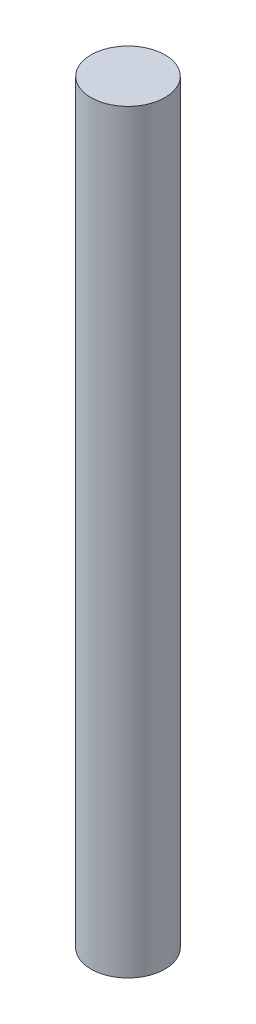
SolidWorks part; units mm, degrees
ref_plane "Front Plane" through (0, 0, 0) normal (0, 0, 1) x (1, 0, 0)
ref_plane "Top Plane" through (0, 0, 0) normal (0, 1, 0) x (1, 0, 0)
ref_plane "Right Plane" through (0, 0, 0) normal (1, 0, 0) x (0, 0, -1)
sketch "Sketch1" plane through (0, 0, 0) normal (0, 1, 0) x (1, 0, 0)
  circle A0 centre (0, 0) radius 12.446
  dimension "D1" = 24.892
extrude "Boss-Extrude1" add sketch "Sketch1" along normal blind 254
ref_axis "center axis" through (0, 254, 0) along (0, -1, 0)
